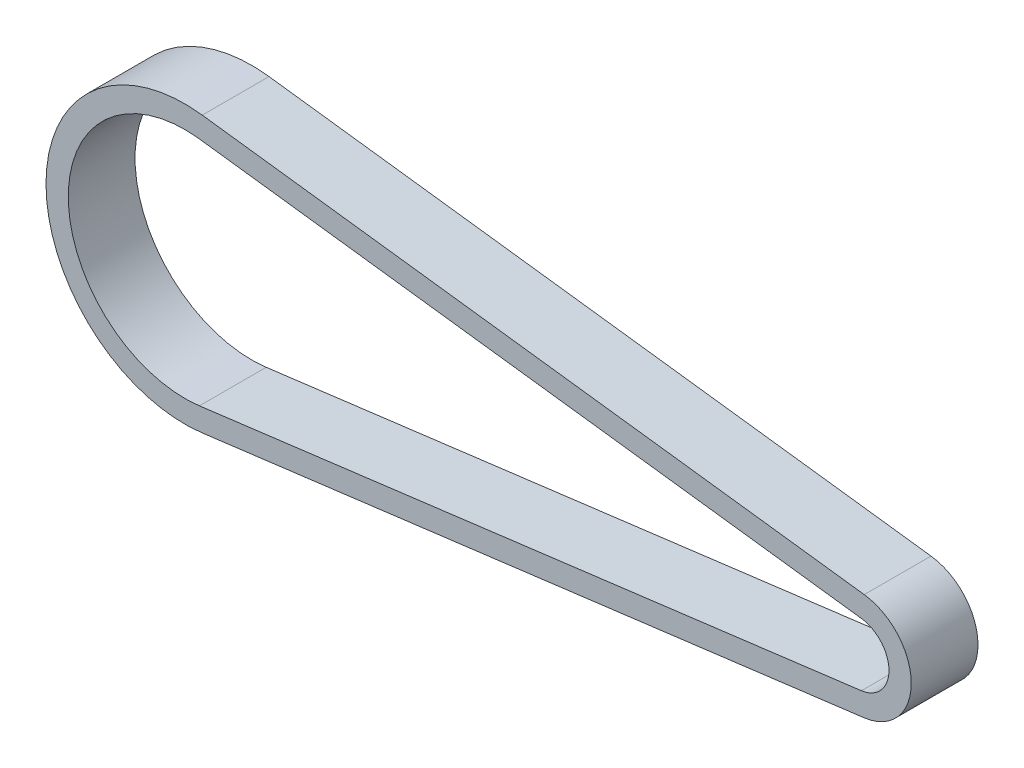
SolidWorks part; units mm, degrees
ref_plane "Plano frontal" through (0, 0, 0) normal (0, 0, 1) x (1, 0, 0)
ref_plane "Plano superior" through (0, 0, 0) normal (0, 1, 0) x (1, 0, 0)
ref_plane "Plano direito" through (0, 0, 0) normal (1, 0, 0) x (0, 0, -1)
sketch "Esboço1" plane through (0, 0, 0) normal (0, 0, 1) x (1, 0, 0)
  line L0 (2.1719, 17.0623) -> (91.4021, 5.704) construction
  line L1 (91.4021, -5.704) -> (2.1719, -17.0623) construction
  line L2 (1.9825, 15.5743) -> (91.2127, 4.216)
  line L3 (91.2127, -4.216) -> (1.9825, -15.5743)
  line L4 (2.3613, 18.5503) -> (91.5915, 7.192)
  line L5 (91.5915, -7.192) -> (2.3613, -18.5503)
  circle A6 centre (0, 0) radius 17.2 construction
  circle A7 centre (90.676, 0) radius 5.75 construction
  circle A8 centre (0, 0) radius 18.7
  circle A9 centre (90.676, 0) radius 7.25
  circle A10 centre (0, 0) radius 15.7
  circle A11 centre (90.676, 0) radius 4.25
  dimension "D1" = 34.4
  dimension "D5" = 1.5
  dimension "D3" = 11.5
  dimension "D2" = 90.676
  dimension "D4" = 1.5
extrude "Ressalto-extrusão1" add sketch "Esboço1" along normal mid plane 9 contours A11 L3 A9 L2 | A9 L3 A8 L5 | A9 L4 A8 L2 | A10 L2 A8 L3 region at (-16.1842, 0, 0) region at (48.1451, 11.2504, 0) region at (88.2849, 6.641, 0) region at (48.1451, -11.2504, 0)
